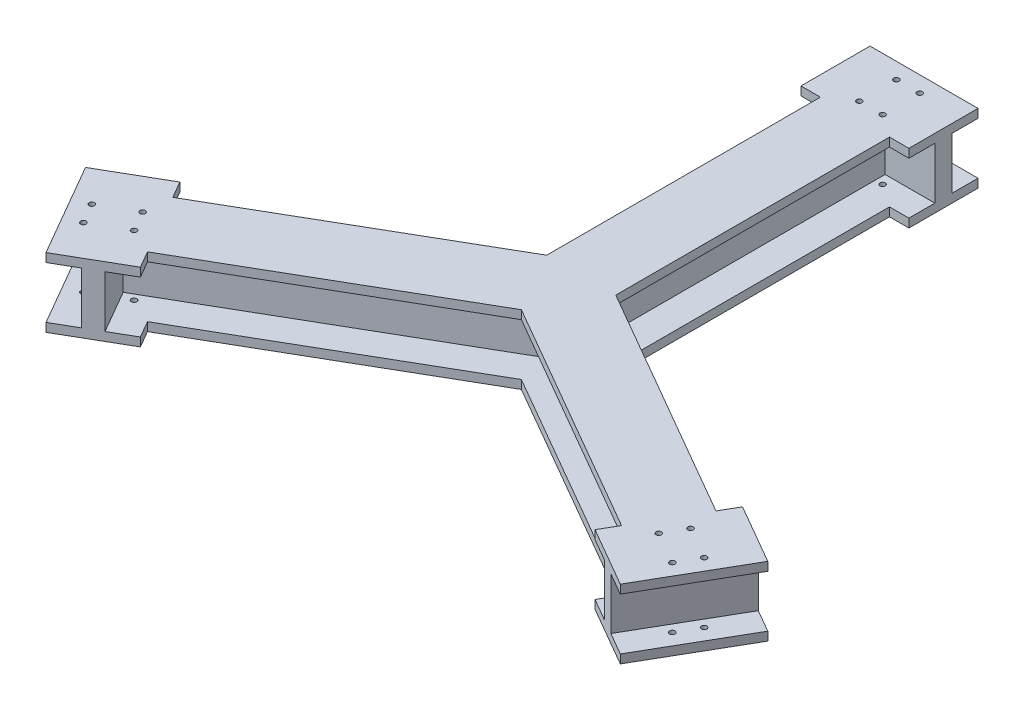
SolidWorks part; units mm, degrees
ref_plane "前基準面" through (0, 0, 0) normal (0, 0, 1) x (1, 0, 0)
ref_plane "上基準面" through (0, 0, 0) normal (0, 1, 0) x (1, 0, 0)
ref_plane "右基準面" through (0, 0, 0) normal (1, 0, 0) x (0, 0, -1)
sketch "草圖1" plane through (0, 0, 0) normal (0, 1, 0) x (1, 0, 0)
  line L0 (0, 0) -> (0, 49000) construction
  line L1 (-866.0254, -500) -> (0, 0) construction
  line L2 (0, 0) -> (42435.2448, -24500) construction
  line L5 (-80, 46.188) -> (-80, 680)
  line L6 (-80, 680) -> (80, 680)
  line L7 (80, 46.188) -> (80, 680)
  line L8 (0, -92.376) -> (-548.8973, -409.282)
  line L9 (-548.8973, -409.282) -> (-628.8973, -270.718)
  line L10 (-628.8973, -270.718) -> (-80, 46.188)
  line L11 (80, 46.188) -> (628.8973, -270.718)
  line L12 (628.8973, -270.718) -> (548.8973, -409.282)
  line L13 (548.8973, -409.282) -> (0, -92.376)
  dimension "D1" = 120
  dimension "D2" = 120
  dimension "D3" = 160
  dimension "D4" = 680
  dimension "D5" = 160
  dimension "D6" = 680
  dimension "D7" = 160
  dimension "D8" = 680
extrude "填料-伸長1" add sketch "草圖1" along normal blind 160
sketch "草圖2" plane through (0, 160, 0) normal (0, 1, 0) x (1, 0, 0)
  line L0 (0, -1000) -> (0, 49000) construction
  line L1 (-125, 680) -> (125, 680)
  line L2 (-125, 680) -> (-125, 840)
  line L3 (-125, 840) -> (125, 840)
  line L4 (125, 680) -> (125, 840)
  line L5 (80, 680) -> (-80, 680) construction
  dimension "D1" = 250
  dimension "D2" = 160
extrude "填料-伸長2" add sketch "草圖2" against normal up to surface (160 mm away) up to face at (0, 0, 0)
ref_axis "基準軸1" through (0, 50, 0) along (0, -1, 0)
pattern_circular "環狀複製排列1" count 3 over 360 about axis through (0, 50, 0) along (0, -1, 0) of "填料-伸長2"
sketch "草圖3" plane through (80, 0, 0) normal (1, 0, 0) x (0, 0, -1)
  line L0 (46.188, 160) -> (46.188, 0) construction
  line L1 (46.188, 140) -> (680, 140)
  line L2 (46.188, 140) -> (46.188, 20)
  line L3 (46.188, 20) -> (680, 20)
  line L4 (680, 140) -> (680, 20)
  line L5 (680, 160) -> (680, 0) construction
  line L6 (46.188, 160) -> (680, 160) construction
  line L7 (46.188, 0) -> (680, 0) construction
  dimension "D1" = 20
  dimension "D2" = 20
extrude "除料-伸長1" cut sketch "草圖3" against normal blind 70
mirror "鏡射1" about plane through (0, 0, 0) normal (1, 0, 0) of "除料-伸長1"
sketch "草圖4" plane through (0, 0, -680) normal (0, 0, 1) x (1, 0, 0)
  line L0 (125, 0) -> (125, 160) construction
  line L1 (125, 140) -> (-125, 140)
  line L2 (125, 140) -> (125, 20)
  line L3 (125, 20) -> (-125, 20)
  line L4 (-125, 140) -> (-125, 20)
  line L5 (-125, 0) -> (-125, 160) construction
  line L6 (125, 160) -> (-125, 160) construction
  line L7 (125, 0) -> (-125, 0) construction
  dimension "D1" = 20
  dimension "D2" = 20
extrude "除料-伸長2" cut sketch "草圖4" against normal blind 60
sketch "草圖5" plane through (0, 0, -840) normal (0, 0, -1) x (-1, 0, 0)
  line L0 (-125, 0) -> (-125, 160) construction
  line L1 (-125, 140) -> (125, 140)
  line L2 (-125, 140) -> (-125, 20)
  line L3 (-125, 20) -> (125, 20)
  line L4 (125, 140) -> (125, 20)
  line L5 (125, 0) -> (125, 160) construction
  line L6 (-125, 160) -> (125, 160) construction
  line L7 (-125, 0) -> (125, 0) construction
  dimension "D1" = 20
  dimension "D2" = 20
extrude "除料-伸長3" cut sketch "草圖5" against normal blind 60
sketch "草圖6" plane through (-10, 0, 0) normal (-1, 0, 0) x (0, 0, 1)
  line L1 (-680, 140) -> (-740, 140)
  line L2 (-680, 140) -> (-680, 20)
  line L3 (-680, 20) -> (-740, 20)
  line L4 (-740, 140) -> (-740, 20)
extrude "填料-伸長3" add sketch "草圖6" against normal up to surface (20 mm away) up to face at (10, 80, -363.094)
pattern_circular "環狀複製排列4" count 3 over 360 about axis through (0, 50, 0) along (0, -1, 0) of "填料-伸長3", "除料-伸長3", "除料-伸長2", "除料-伸長1", "鏡射1"
sketch "草圖7" plane through (0, 20, 0) normal (0, 1, 0) x (1, 0, 0)
  line L0 (-10, 46.188) -> (-80, 46.188)
  line L1 (-80, 46.188) -> (-45, -14.4338)
  line L2 (-45, -14.4338) -> (-10, 5.7735)
  line L3 (-10, 5.7735) -> (-10, 46.188)
  line L4 (10, 46.188) -> (80, 46.188)
  line L5 (80, 46.188) -> (45, -14.4338)
  line L6 (45, -14.4338) -> (10, 5.7735)
  line L7 (10, 5.7735) -> (10, 46.188)
  line L8 (-35, -31.7543) -> (0, -11.547)
  line L9 (-35, -31.7543) -> (0, -92.376)
  line L10 (0, -92.376) -> (35, -31.7543)
  line L11 (35, -31.7543) -> (0, -11.547)
extrude "除料-伸長4" cut sketch "草圖7" along normal up to surface (120 mm away)
hole_wizard "M14x1.5 螺紋孔1" positions "草圖9" profile "草圖8" tap size "M14x1.5" standard "ISO" end condition through all
sketch "草圖9" plane through (0, 160, 0) normal (0, 1, 0) x (-1, 0, 0)
  line L0 (0, -1840) -> (0, 48160) construction
  line L1 (-125, -840) -> (125, -840) construction
  line L2 (-875, -760) -> (49125, -760) construction
  line L3 (125, -840) -> (125, -680) construction
  point P0 (27, -803)
  point P1 (-27, -803)
  point P3 (-27, -717)
  point P5 (27, -717)
  point P14 (0, -840)
  point P21 (125, -760)
  dimension "D1" = 54
  dimension "D2" = 86
sketch "草圖8" plane through (-27, 160, -803) normal (1, 0, 0) x (0, 0, 1)
  line L0 (0, 0) -> (0, 160.0001)
  line L1 (0, 160.0001) -> (6.25, 160.0001)
  line L2 (6.25, 160.0001) -> (6.25, 0)
  line L5 (6.25, 0) -> (0, 0)
  line L11 (0, -6.35) -> (0, 107.95) construction
  dimension "貫穿螺孔鑽直徑" = 12.5
  dimension "貫穿螺孔鑽深度" = 160.0001
cosmetic thread "鑽孔螺紋1" parameters "D2"=14
cosmetic thread "鑽孔螺紋2" parameters "D2"=14
cosmetic thread "鑽孔螺紋3" parameters "D2"=14
cosmetic thread "鑽孔螺紋4" parameters "D2"=14
pattern_circular "環狀複製排列5" count 3 over 360 about axis through (0, 50, 0) along (0, -1, 0) of "M14x1.5 螺紋孔1"
